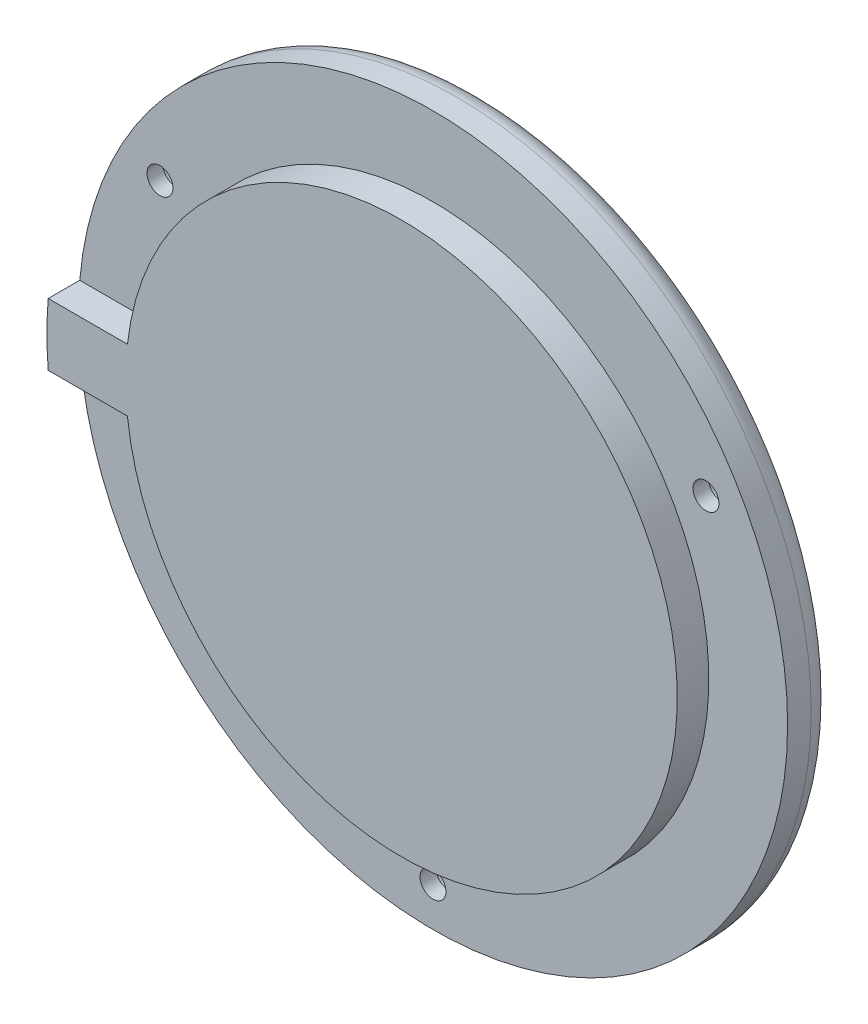
SolidWorks part; units mm, degrees
ref_plane "Plano frontal" through (0, 0, 0) normal (0, 0, 1) x (1, 0, 0)
ref_plane "Plano superior" through (0, 0, 0) normal (0, 1, 0) x (1, 0, 0)
ref_plane "Plano direito" through (0, 0, 0) normal (1, 0, 0) x (0, 0, -1)
sketch "Esboço1" plane through (0, 0, 0) normal (0, 0, 1) x (1, 0, 0)
  circle A0 centre (0, 0) radius 45
  dimension "D1" = 90
extrude "Ressalto-extrusão1" add sketch "Esboço1" along normal blind 6
sketch "Esboço3" plane through (0, 0, 6) normal (0, 0, 1) x (1, 0, 0)
  line L3 (-34.7764, 3.95) -> (-44.8263, 3.95)
  line L5 (-34.7764, -3.95) -> (-44.8263, -3.95)
  arc A0 (-34.7764, -3.95) -> (-34.7764, 3.95) centre (0, 0) ccw
  arc A1 (-44.8263, 3.95) -> (-44.8263, -3.95) centre (0, 0) ccw
  dimension "D1" = 90
  dimension "D2" = 70
  dimension "D3" = 10.0499
  dimension "D4" = 10.0499
extrude "Ressalto-extrusão2" add sketch "Esboço3" along normal blind 4
sketch "Esboço4" plane through (0, 0, 6) normal (0, 0, 1) x (1, 0, 0)
  circle A0 centre (0, -40) radius 1.65
  arc A1 (-44.8263, -3.95) -> (-44.8263, 3.95) centre (0, 0) ccw construction
  circle A2 centre (-34.641, 20) radius 1.65
  circle A3 centre (34.641, 20) radius 1.65
  point P6 (45, 0)
  point P14 (0, 0)
  dimension "D1" = 3.3
  dimension "D5" = 60
  dimension "D2" = 40
  dimension "D3" = 45
  dimension "D6" = 69.282
  dimension "D4" = 3
extrude "Corte-extrusão1" cut sketch "Esboço4" against normal blind 2
sketch "Esboço5" plane through (0, 0, 4) normal (0, 0, 1) x (1, 0, 0)
  circle A0 centre (0, -40) radius 2.95
  circle A1 centre (-34.641, 20) radius 2.95
  circle A2 centre (34.641, 20) radius 2.95
  point P10 (0, 0)
  dimension "D1" = 5.9
  dimension "D2" = 3
  dimension "D3" = 69.282
  dimension "D4" = 60
extrude "Corte-extrusão2" cut sketch "Esboço5" against normal up to surface (4 mm away) up to face at (45, 0, 0)
fillet "Filete1" radius 3 1 edges at (45, 0, 0)
